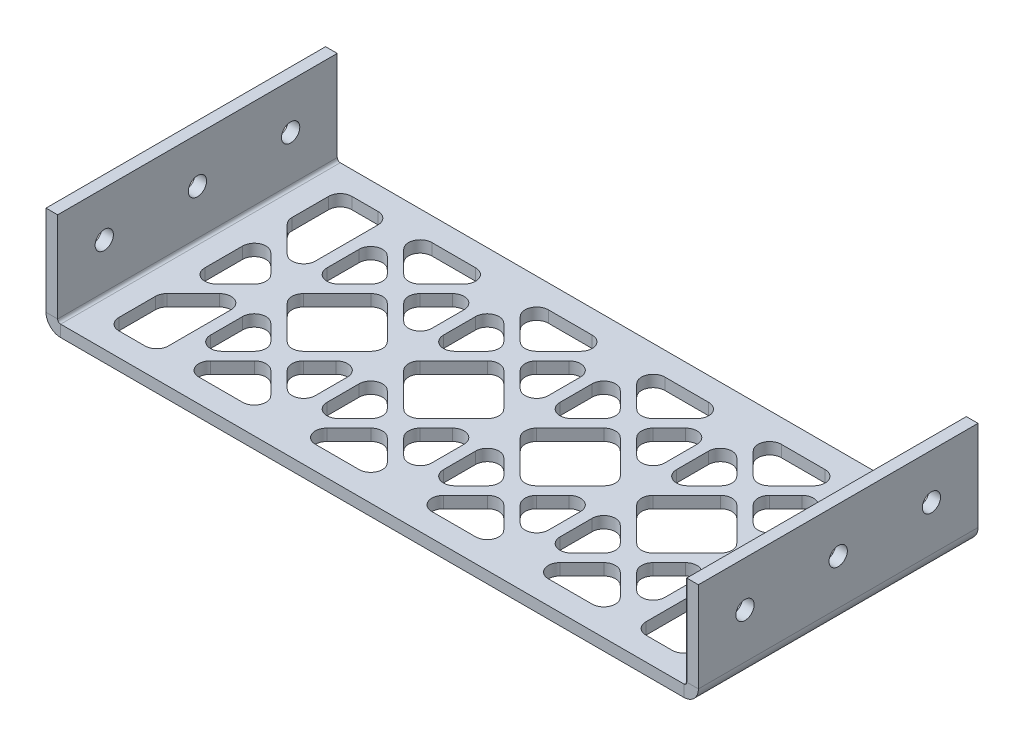
SolidWorks part; units mm, degrees
note: The reader was unsure of these and kept them because the rebuilt part matched: bend radius of "Base-Flange2", "BaseBend3", "BaseBend4".
ref_plane "Front Plane" through (0, 0, 0) normal (0, 0, 1) x (1, 0, 0)
ref_plane "Top Plane" through (0, 0, 0) normal (0, 1, 0) x (1, 0, 0)
ref_plane "Right Plane" through (0, 0, 0) normal (1, 0, 0) x (0, 0, -1)
sketch "Sketch1" plane through (0, 0, 0) normal (0, 0, 1) x (1, 0, 0)
  line L0 (-85.725, 0) -> (85.725, 0)
  line L1 (-85.725, 0) -> (-85.725, 25.4)
  line L2 (85.725, 0) -> (85.725, 25.4)
  point P3 (0, 0)
  dimension "D1" = 171.45
  dimension "D2" = 25.4
base flange "Base-Flange2" sketch "Sketch1" end condition mid plane depth 76.2 reverse direction no thickness 3.175 reverse thickness direction no bend radius 0.8128
bend "BaseBend3" bend radius 0.8128 bend angle 90 parameters "D5"=1
bend "BaseBend4" bend radius 0.8128 bend angle 90 parameters "D5"=2
sketch "Sketch8" plane through (-85.725, 0, 0) normal (1, 0, 0) x (0, 0, -1)
  line L0 (38.1, 25.4) -> (38.1, 0.8128) construction
  circle A0 centre (-25.4, 13.1064) radius 2.4892
  circle A1 centre (0, 13.1064) radius 2.4892
  circle A2 centre (25.4, 13.1064) radius 2.4892
  point P8 (38.1, 13.1064)
  point P9 (0, 15.7087)
  dimension "D1" = 4.9784
  dimension "D2" = 25.4
  dimension "D3" = 12.7
  dimension "D4" = 25.4
extrude "Cut-Extrude1" cut sketch "Sketch8" against normal through all and the other way through all normal cut yes
sketch "Sketch9" plane through (0, -3.175, 0) normal (0, -1, 0) x (1, 0, 0)
  line L0 (-31.75, -31.75) -> (-31.75, 31.75) construction
  line L1 (31.75, -31.75) -> (31.75, 31.75) construction
  line L2 (0, -31.75) -> (0, 31.75) construction
  line L3 (63.5, -31.75) -> (0, 31.75) construction
  line L4 (0, -31.75) -> (0, 31.75) construction
  line L5 (31.75, 31.75) -> (-31.75, -31.75) construction
  line L6 (31.75, -31.75) -> (-31.75, 31.75) construction
  line L7 (63.5, 31.75) -> (0, -31.75) construction
  line L8 (-78.5622, -31.75) -> (78.5622, -31.75)
  line L9 (78.5622, -31.75) -> (78.5622, 31.75)
  line L10 (78.5622, 31.75) -> (-78.5622, 31.75)
  line L11 (-78.5622, 31.75) -> (-78.5622, -31.75)
  line L12 (-78.5622, -31.75) -> (78.5622, -31.75)
  line L13 (78.5622, -31.75) -> (78.5622, 31.75)
  line L14 (78.5622, 31.75) -> (-78.5622, 31.75)
  line L15 (-78.5622, 31.75) -> (-78.5622, -31.75)
  line L16 (31.75, -31.75) -> (31.75, 31.75) construction
  line L17 (63.5, -31.75) -> (63.5, 31.75) construction
  line L18 (31.75, -31.75) -> (31.75, 31.75) construction
  line L19 (95.25, -31.75) -> (31.75, 31.75) construction
  line L20 (95.25, 31.75) -> (31.75, -31.75) construction
  line L21 (63.5, -31.75) -> (63.5, 31.75) construction
  line L22 (95.25, -31.75) -> (95.25, 31.75) construction
  line L23 (-31.75, -31.75) -> (-31.75, 31.75) construction
  line L24 (31.75, -31.75) -> (-31.75, 31.75) construction
  line L25 (31.75, 31.75) -> (-31.75, -31.75) construction
  line L26 (0, -31.75) -> (0, 31.75) construction
  line L27 (31.75, -31.75) -> (31.75, 31.75) construction
  line L28 (0, -31.75) -> (0, 31.75) construction
  line L29 (63.5, -31.75) -> (0, 31.75) construction
  line L30 (63.5, 31.75) -> (0, -31.75) construction
  line L31 (31.75, -31.75) -> (31.75, 31.75) construction
  line L32 (63.5, -31.75) -> (63.5, 31.75) construction
  line L33 (-63.5, -31.75) -> (-63.5, 31.75) construction
  line L34 (0, -31.75) -> (-63.5, 31.75) construction
  line L35 (0, 31.75) -> (-63.5, -31.75) construction
  line L36 (-31.75, -31.75) -> (-31.75, 31.75) construction
  line L37 (0, -31.75) -> (0, 31.75) construction
  line L38 (-31.75, -31.75) -> (-31.75, 31.75) construction
  line L39 (31.75, -31.75) -> (-31.75, 31.75) construction
  line L40 (31.75, 31.75) -> (-31.75, -31.75) construction
  line L41 (0, -31.75) -> (0, 31.75) construction
  line L42 (31.75, -31.75) -> (31.75, 31.75) construction
  line L43 (-63.5, -31.75) -> (-63.5, 31.75) construction
  line L44 (0, -31.75) -> (-63.5, 31.75) construction
  line L45 (0, 31.75) -> (-63.5, -31.75) construction
  line L46 (-31.75, -31.75) -> (-31.75, 31.75) construction
  line L47 (0, -31.75) -> (0, 31.75) construction
  line L48 (-95.25, -31.75) -> (-95.25, 31.75) construction
  line L49 (-31.75, -31.75) -> (-95.25, 31.75) construction
  line L50 (-31.75, 31.75) -> (-95.25, -31.75) construction
  line L51 (-63.5, -31.75) -> (-63.5, 31.75) construction
  line L52 (-31.75, -31.75) -> (-31.75, 31.75) construction
  line L53 (-32.8725, 32.8725) -> (-96.3725, -30.6275)
  line L54 (-30.6275, -30.6275) -> (-94.1275, 32.8725)
  line L55 (-1.1225, 32.8725) -> (-61.9125, -27.9174)
  line L56 (-61.9125, -27.9174) -> (-61.9125, 31.75)
  line L57 (1.1225, -30.6275) -> (-62.3775, 32.8725)
  line L58 (33.3375, -31.75) -> (33.3375, 35.5826)
  line L59 (33.3375, 35.5826) -> (-30.1625, -27.9174)
  line L60 (-30.1625, -27.9174) -> (-30.1625, 31.75)
  line L61 (32.8725, -30.6275) -> (-30.6275, 32.8725)
  line L62 (65.0875, -31.75) -> (65.0875, 35.5826)
  line L63 (65.0875, 35.5826) -> (1.5875, -27.9174)
  line L64 (1.5875, -27.9174) -> (1.5875, 31.75)
  line L65 (64.6225, -30.6275) -> (1.1225, 32.8725)
  line L66 (96.3725, -30.6275) -> (32.8725, 32.8725)
  line L67 (94.1275, 32.8725) -> (30.6275, -30.6275)
  line L68 (-30.6275, 30.6275) -> (-94.1275, -32.8725)
  line L69 (-32.8725, -32.8725) -> (-96.3725, 30.6275)
  line L70 (1.1225, 30.6275) -> (-65.0875, -35.5826)
  line L71 (-65.0875, -35.5826) -> (-65.0875, 31.75)
  line L72 (-1.1225, -32.8725) -> (-64.6225, 30.6275)
  line L73 (30.1625, -31.75) -> (30.1625, 27.9174)
  line L74 (30.1625, 27.9174) -> (-33.3375, -35.5826)
  line L75 (-33.3375, -35.5826) -> (-33.3375, 31.75)
  line L76 (30.6275, -32.8725) -> (-32.8725, 30.6275)
  line L77 (61.9125, -31.75) -> (61.9125, 27.9174)
  line L78 (61.9125, 27.9174) -> (-1.5875, -35.5826)
  line L79 (-1.5875, -35.5826) -> (-1.5875, 31.75)
  line L80 (62.3775, -32.8725) -> (-1.1225, 30.6275)
  line L81 (94.1275, -32.8725) -> (30.6275, 30.6275)
  line L82 (96.3725, 30.6275) -> (32.8725, -32.8725)
  point P7 (0, 0)
  dimension "D2" = 45
  dimension "D3" = 90
  dimension "D4" = 3
  dimension "D5" = 3
  dimension "D6" = 31.75
  dimension "D1" = 6.35
  dimension "D7" = 1.5875
  dimension "D8" = 1.5875
extrude "Cut-Extrude2" cut sketch "Sketch9" against normal through all both and the other way through all contours L13 L82 L66 | L13 L81 L62 L12 | L67 L13 L14 L62 | L67 L81 L78 L65 | L77 L82 L65 | L80 L82 L12 | L77 L78 L66 | L66 L63 L14 | L63 L81 L58 | L67 L80 L58 | L73 L78 L61 | L76 L78 L12 | L63 L80 L74 L61 | L73 L74 L65 | L65 L59 L14 | L59 L80 L64 | L63 L76 L64 | L72 L74 L12 | L59 L76 L70 L57 | L57 L79 L74 | L61 L79 L70 | L61 L55 L14 | L55 L76 L60 | L57 L75 L68 | L55 L72 L68 L54 | L54 L75 L70 | L59 L72 L60 | L69 L70 L12 | L55 L69 L56 | L53 L72 L56 | L57 L53 L14 | L54 L71 L14 L15 | L53 L69 L15 | L12 L71 L68 L15 normal cut yes
fillet "Fillet1" radius 3.175 110 edges at (2.2451, -1.5875, 0) (15.875, -1.5875, 13.6299) (29.5049, -1.5875, 0) (15.875, -1.5875, -13.6299) (33.3375, -1.5875, -3.8326) (45.3799, -1.5875, -15.875) (33.3375, -1.5875, -27.9174) (1.5875, -1.5875, -3.8326) (13.6299, -1.5875, -15.875) (1.5875, -1.5875, -27.9174) (1.5875, -1.5875, 27.9174) (13.6299, -1.5875, 15.875) (1.5875, -1.5875, 3.8326) (29.5049, -1.5875, 31.75) (15.875, -1.5875, 18.1201) (2.2451, -1.5875, 31.75) (65.0875, -1.5875, 31.75) (78.5622, -1.5875, 31.75) (78.5622, -1.5875, 17.3073) (65.0875, -1.5875, 3.8326) (33.9951, -1.5875, 0) (47.625, -1.5875, 13.6299) (61.2549, -1.5875, 0) (47.625, -1.5875, -13.6299) (61.2549, -1.5875, 31.75) (47.625, -1.5875, 18.1201) (33.9951, -1.5875, 31.75) (33.3375, -1.5875, 27.9174) (45.3799, -1.5875, 15.875) (33.3375, -1.5875, 3.8326) (-61.9125, -1.5875, -3.8326) (-49.8701, -1.5875, -15.875) (-61.9125, -1.5875, -27.9174) (-30.1625, -1.5875, -3.8326) (-18.1201, -1.5875, -15.875) (-30.1625, -1.5875, -27.9174) (-33.3375, -1.5875, -3.8326) (-33.3375, -1.5875, -27.9174) (-45.3799, -1.5875, -15.875) (-33.9951, -1.5875, 31.75) (-47.625, -1.5875, 18.1201) (-61.2549, -1.5875, 31.75) (-61.9125, -1.5875, 27.9174) (-49.8701, -1.5875, 15.875) (-61.9125, -1.5875, 3.8326) (-78.5622, -1.5875, 12.8171) (-65.7451, -1.5875, 0) (-78.5622, -1.5875, -12.8171) (-78.5622, -1.5875, 31.75) (-65.0875, -1.5875, 31.75) (-65.0875, -1.5875, 3.8326) (-78.5622, -1.5875, 17.3073) (-1.5875, -1.5875, 27.9174) (-1.5875, -1.5875, 3.8326) (-13.6299, -1.5875, 15.875) (-1.5875, -1.5875, -3.8326) (-1.5875, -1.5875, -27.9174) (-13.6299, -1.5875, -15.875) (-29.5049, -1.5875, 0) (-15.875, -1.5875, 13.6299) (-2.2451, -1.5875, 0) (-15.875, -1.5875, -13.6299) (-30.1625, -1.5875, 27.9174) (-18.1201, -1.5875, 15.875) (-30.1625, -1.5875, 3.8326) (-2.2451, -1.5875, 31.75) (-15.875, -1.5875, 18.1201) (-29.5049, -1.5875, 31.75) (-61.2549, -1.5875, 0) (-47.625, -1.5875, 13.6299) (-33.9951, -1.5875, 0) (-47.625, -1.5875, -13.6299) (-33.3375, -1.5875, 27.9174) (-33.3375, -1.5875, 3.8326) (-45.3799, -1.5875, 15.875) (78.5622, -1.5875, -12.8171) (65.7451, -1.5875, 0) (78.5622, -1.5875, 12.8171) (-78.5622, -1.5875, -31.75) (-78.5622, -1.5875, -17.3073) (-65.0875, -1.5875, -3.8326) (-65.0875, -1.5875, -31.75) (-2.2451, -1.5875, -31.75) (-29.5049, -1.5875, -31.75) (-15.875, -1.5875, -18.1201) (-33.9951, -1.5875, -31.75) (-61.2549, -1.5875, -31.75) (-47.625, -1.5875, -18.1201) (61.2549, -1.5875, -31.75) (33.9951, -1.5875, -31.75) (47.625, -1.5875, -18.1201) (61.9125, -1.5875, 3.8326) (49.8701, -1.5875, 15.875) (61.9125, -1.5875, 27.9174) (61.9125, -1.5875, -27.9174) (49.8701, -1.5875, -15.875) (61.9125, -1.5875, -3.8326) (65.0875, -1.5875, -31.75) (65.0875, -1.5875, -3.8326) (78.5622, -1.5875, -17.3073) (30.1625, -1.5875, 3.8326) (18.1201, -1.5875, 15.875) (30.1625, -1.5875, 27.9174) (30.1625, -1.5875, -27.9174) (18.1201, -1.5875, -15.875) (30.1625, -1.5875, -3.8326) (29.5049, -1.5875, -31.75) (2.2451, -1.5875, -31.75) (15.875, -1.5875, -18.1201) (78.5622, -1.5875, -31.75)
sketch "Bend-Lines1" [suppressed] plane through (0, 0, 0) normal (0, 1, 0) x (1, 0, 0)
sketch "Bounding-Box1" [suppressed] plane through (0, 0, 0) normal (0, 1, 0) x (1, 0, 0)
sheet metal parameters "Sheet-Metal2" thickness 3.175 parameters "D1"=0.8128
flat pattern "Flat-Pattern2" [suppressed]
sketch "Bend-Lines3" plane through (0, 0, 0) normal (0, 1, 0) x (1, 0, 0)
  line L0 (-86.3485, -38.1) -> (-86.3485, 38.1) construction
  line L1 (86.3485, 38.1) -> (86.3485, -38.1) construction
  line L2 (-86.3485, -38.1) -> (-86.3485, 38.1) construction
  line L3 (86.3485, 38.1) -> (86.3485, -38.1) construction
sketch3d "Bounding-Box3" [suppressed]
  line L0 (198.0971, 76.2, 0) -> (-26.6471, 76.2, 0) construction
  line L1 (198.0971, 0, 0) -> (-26.6471, 0, 0) construction
  line L2 (198.0971, 76.2, 0) -> (198.0971, 0, 0) construction
  line L3 (-26.6471, 76.2, 0) -> (-26.6471, 0, 0) construction
bend of the flat pattern "Flatten-<BaseBend3>1"
bend of the flat pattern "Flatten-<BaseBend4>1"
sheet metal parameters "Sheet-Metal3" thickness 3.175 parameters "D1"=0.8128
flat pattern "Flat-Pattern2"
sketch "Bend-Lines3" plane through (0, 0, 0) normal (0, 1, 0) x (1, 0, 0)
  line L0 (-86.3485, -38.1) -> (-86.3485, 38.1) construction
  line L1 (86.3485, 38.1) -> (86.3485, -38.1) construction
  line L2 (-86.3485, -38.1) -> (-86.3485, 38.1) construction
  line L3 (86.3485, 38.1) -> (86.3485, -38.1) construction
sketch3d "Bounding-Box3" [suppressed]
  line L0 (198.0971, 76.2, 0) -> (-26.6471, 76.2, 0) construction
  line L1 (198.0971, 0, 0) -> (-26.6471, 0, 0) construction
  line L2 (198.0971, 76.2, 0) -> (198.0971, 0, 0) construction
  line L3 (-26.6471, 76.2, 0) -> (-26.6471, 0, 0) construction
bend of the flat pattern "Flatten-<BaseBend3>1"
bend of the flat pattern "Flatten-<BaseBend4>1"
sheet metal parameters "Sheet-Metal4" thickness 3.175 parameters "D1"=0.8128
flat pattern "Flat-Pattern2"
sketch "Bend-Lines3" plane through (0, 0, 0) normal (0, 1, 0) x (1, 0, 0)
  line L0 (-86.3485, -38.1) -> (-86.3485, 38.1) construction
  line L1 (86.3485, 38.1) -> (86.3485, -38.1) construction
  line L2 (-86.3485, -38.1) -> (-86.3485, 38.1) construction
  line L3 (86.3485, 38.1) -> (86.3485, -38.1) construction
sketch3d "Bounding-Box3" [suppressed]
  line L0 (198.0971, 76.2, 0) -> (-26.6471, 76.2, 0) construction
  line L1 (198.0971, 0, 0) -> (-26.6471, 0, 0) construction
  line L2 (198.0971, 76.2, 0) -> (198.0971, 0, 0) construction
  line L3 (-26.6471, 76.2, 0) -> (-26.6471, 0, 0) construction
bend of the flat pattern "Flatten-<BaseBend3>1"
bend of the flat pattern "Flatten-<BaseBend4>1"
